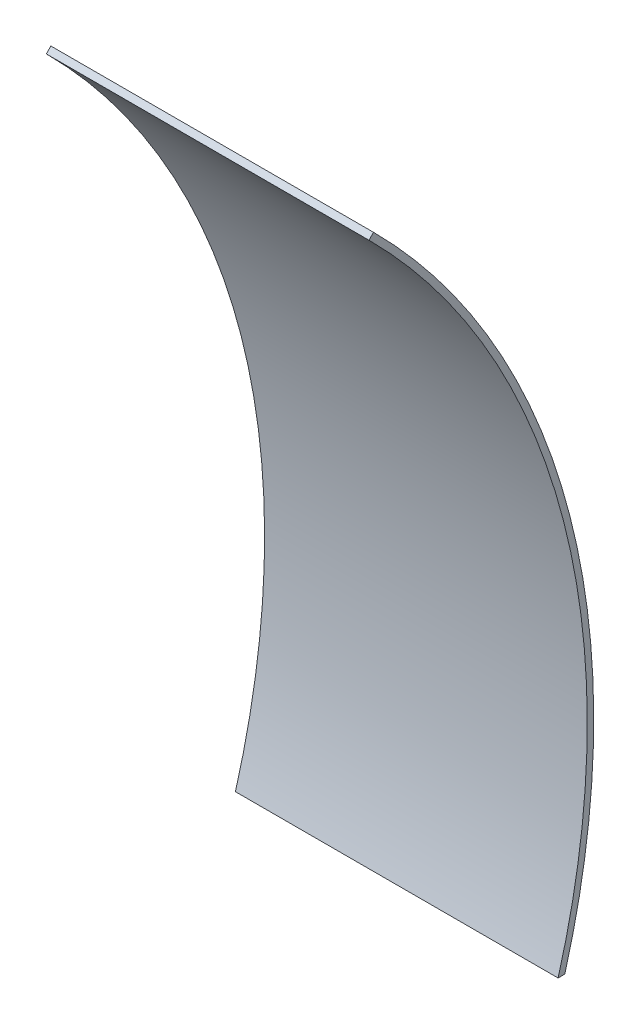
SolidWorks part; units mm, degrees
material "PE High Density"
ref_plane "Front Plane" through (0, 0, 0) normal (0, 0, 1) x (1, 0, 0)
ref_plane "Top Plane" through (0, 0, 0) normal (0, 1, 0) x (1, 0, 0)
ref_plane "Right Plane" through (0, 0, 0) normal (1, 0, 0) x (0, 0, -1)
sketch "Sketch1" plane through (0, 0, 0) normal (1, 0, 0) x (0, 0, -1)
  line L0 (0, 0) -> (183.3562, 0) construction
  line L1 (0, 0) -> (129.6524, 129.6524) construction
  line L2 (183.3562, 0) -> (183.3562, -50.8) construction
  line L3 (183.3562, -50.8) -> (176.1785, -50.8) construction
  line L4 (129.6524, 129.6524) -> (130.775, 130.775) construction
  line L5 (176.1785, -50.8) -> (177.8301, -50.8)
  line L6 (129.6524, 129.6524) -> (130.775, 130.775)
  arc A0 (183.3562, 0) -> (129.6524, 129.6524) centre (0, 0) ccw
  arc A1 (183.3562, 0) -> (176.1785, -50.8) centre (0, 0) cw
  arc A2 (177.8301, -50.8) -> (130.775, 130.775) centre (0, 0) ccw
  dimension "D2" = 45
  dimension "D4" = 1.5875
  dimension "D1" = 183.3562
  dimension "D3" = 50.8
extrude "Boss-Extrude1" add sketch "Sketch1" along normal blind 79.375
